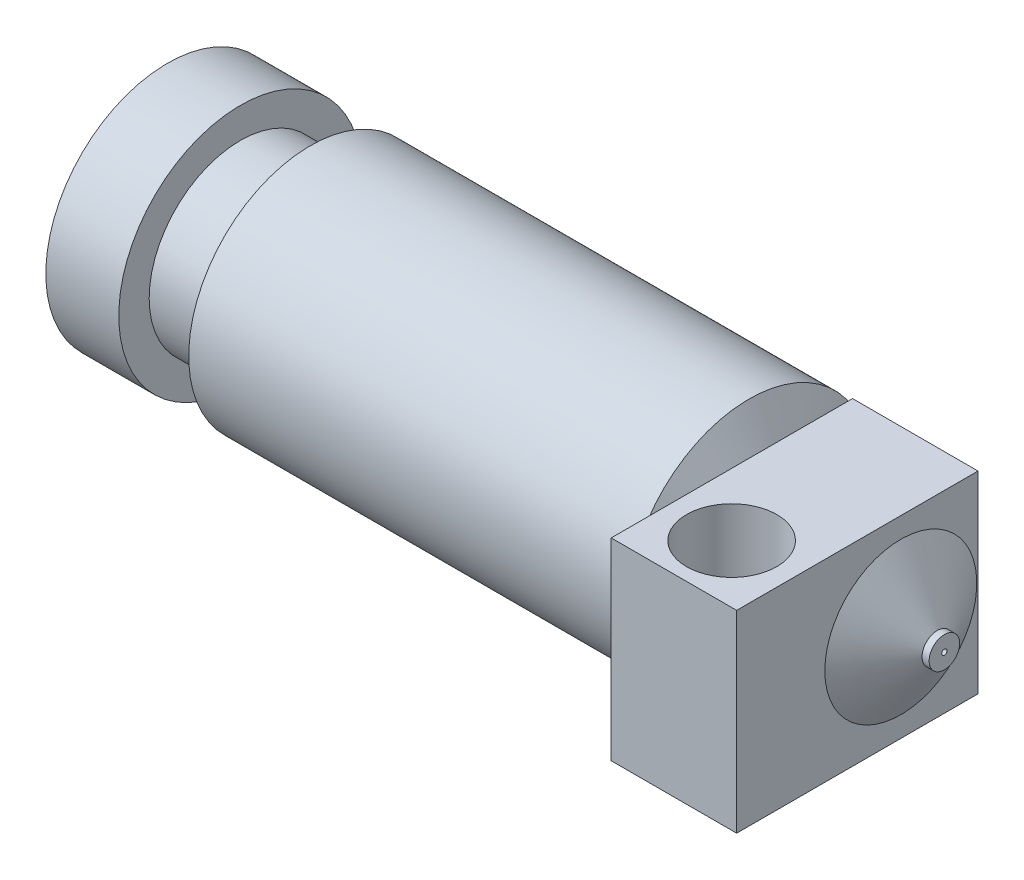
SolidWorks part; units mm, degrees
ref_plane "Front Plane" through (0, 0, 0) normal (0, 0, 1) x (1, 0, 0)
ref_plane "Top Plane" through (0, 0, 0) normal (0, 1, 0) x (1, 0, 0)
ref_plane "Right Plane" through (0, 0, 0) normal (1, 0, 0) x (0, 0, -1)
sketch "Sketch1" plane through (0, 0, 0) normal (0, 1, 0) x (1, 0, 0)
  line L0 (0, 0) -> (-40, 0) construction
  line L1 (-40, 8) -> (-35.2, 8)
  line L2 (-40, 8) -> (0, 8) construction
  line L3 (-40, 8) -> (-40, -8) construction
  line L4 (-40, -8) -> (0, -8) construction
  line L5 (0, 8) -> (0, -8) construction
  line L6 (-35.2, 8) -> (-35.2, 6)
  line L7 (-35.2, 6) -> (-30.6, 6)
  line L8 (-30.6, 6) -> (-30.6, 8)
  line L9 (-30.6, 8) -> (-1.7321, 8)
  line L10 (-1.7321, 8) -> (0, 5)
  line L11 (0, 5) -> (0, -5) construction
  line L12 (0, -5) -> (-1.7321, -8) construction
  line L13 (-1.7321, -8) -> (-30.6, -8) construction
  line L14 (-30.6, -8) -> (-30.6, -6) construction
  line L15 (-30.6, -6) -> (-35.2, -6) construction
  line L16 (-35.2, -6) -> (-35.2, -8) construction
  line L17 (-35.2, -8) -> (-40, -8) construction
  line L18 (-40, 3.25) -> (0, 3.25) construction
  line L19 (-40, -3.25) -> (0, -3.25) construction
  line L20 (-40, 8) -> (-40, 3.25)
  line L21 (-40, 3.25) -> (0, 3.25)
  line L22 (0, 3.25) -> (0, 5) construction
  line L23 (0, 5) -> (8.255, 5)
  line L24 (8.255, 5) -> (10.6554, 1.005)
  line L25 (10.6554, 1.005) -> (11.1229, 1.005)
  line L26 (11.1229, 0.175) -> (9.1125, 0.175)
  line L27 (9.1125, 0.175) -> (7.2649, 3.25)
  line L28 (7.2649, 3.25) -> (0, 3.25)
  line L29 (9.1125, 0.175) -> (9.1125, -0.175) construction
  line L30 (9.1125, -0.175) -> (11.1229, -0.175) construction
  line L31 (11.1229, -0.175) -> (11.1229, 0.175) construction
  line L32 (11.1229, 1.005) -> (11.1229, 0.175)
  line L33 (9.1125, -0.175) -> (9.1125, -1.005) construction
  line L34 (9.1125, -1.005) -> (11.1229, -1.005) construction
  line L35 (11.1229, -1.005) -> (11.1229, -0.175) construction
  line L36 (7.2649, 3.25) -> (7.2649, 5) construction
  line L37 (7.2649, 3.25) -> (8.7649, 4.1513) construction
  line L38 (8.255, 5) -> (8.255, -5) construction
  line L39 (8.255, -5) -> (0, -5) construction
  line L40 (8.255, -5) -> (10.6554, -1.005) construction
  dimension "D1" = 16
  dimension "D2" = 40
  dimension "D3" = 10
  dimension "D4" = 12
  dimension "D5" = 30
  dimension "D6" = 4.8
  dimension "D7" = 4.6
  dimension "D8" = 6.5
  dimension "D9" = 2.01
  dimension "D10" = 0.35
  dimension "D11" = 0.4675
  dimension "D12" = 8.255
  dimension "D13" = 118
ref_axis "Axis1" through (0, 0, 0) along (-1, 0, 0)
revolve "Revolve1" add sketch "Sketch1" angle 360 about L0
sketch "Sketch2" plane through (0, 0, 0) normal (1, 0, 0) x (0, 0, -1)
  line L0 (0, 0) -> (-10.8, 0) construction
  line L1 (0, 0) -> (5.08, 0) construction
  line L2 (0, 0) -> (0, 6.35) construction
  line L3 (0, 0) -> (0, -6.35) construction
  line L5 (-10.8, 6.35) -> (5.08, 6.35)
  line L6 (-10.8, 6.35) -> (-10.8, -6.35)
  line L7 (-10.8, -6.35) -> (5.08, -6.35)
  line L8 (5.08, 6.35) -> (5.08, -6.35)
  circle A0 centre (0, 0) radius 3.25
  dimension "D1" = 12.7
  dimension "D2" = 15.88
  dimension "D3" = 5.08
extrude "Boss-Extrude1" add sketch "Sketch2" along normal up to vertex (8.255 mm away) up to point (8.255, 0, -5)
sketch "Sketch3" plane through (0, 6.35, 0) normal (0, 1, 0) x (1, 0, 0)
  line L0 (8.255, -10.8) -> (0, -10.8) construction
  line L1 (8.255, 5.08) -> (8.255, -10.8) construction
  circle A0 centre (4.115, -6.99) radius 2.97
  dimension "D1" = 5.94
  dimension "D2" = 3.81
  dimension "D3" = 4.14
extrude "Cut-Extrude1" cut sketch "Sketch3" against normal through all
ref_plane "Plane1" through (-35.2, 0, 0) normal (1, 0, 0) x (0, 0, -1)
